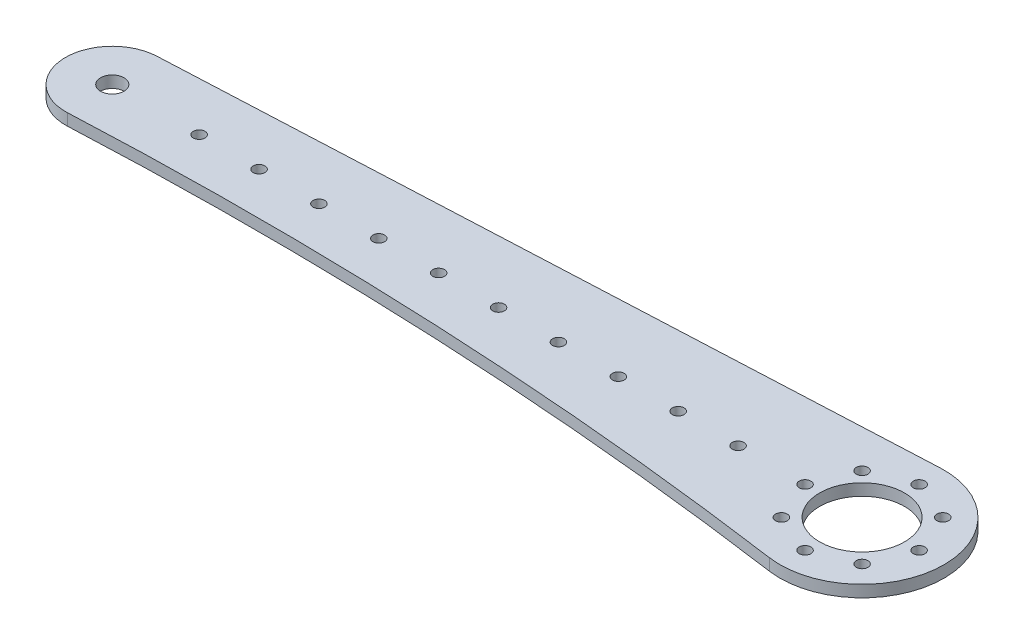
SolidWorks part; units mm, degrees
material "ABS"
ref_plane "Front Plane" through (0, 0, 0) normal (0, 0, 1) x (1, 0, 0)
ref_plane "Top Plane" through (0, 0, 0) normal (0, 1, 0) x (1, 0, 0)
ref_plane "Right Plane" through (0, 0, 0) normal (1, 0, 0) x (0, 0, -1)
sketch "Sketch2" plane through (0, 0, 0) normal (0, 1, 0) x (1, 0, 0)
  line L0 (-203.7953, 12.686) -> (-1.0418, 22.2006)
  line L1 (-1.0418, 22.2006) -> (0, 0) construction
  line L2 (-203.7953, 12.686) -> (-202.6047, -12.686) construction
  circle A0 centre (-203.2, 0) radius 12.7 construction
  circle A1 centre (0, 0) radius 22.225 construction
  circle A2 centre (-0.4465, 9.5145) radius 12.7 construction
  arc A3 (-203.7953, 12.686) -> (-202.6047, -12.686) centre (-203.2, 0) ccw
  arc A4 (-202.6047, -12.686) -> (-3.1072, -22.0067) centre (-152.5116, -1080.1634) cw
  arc A5 (-1.0418, 22.2006) -> (-3.1072, -22.0067) centre (0, 0) cw
  circle A6 centre (0, 0) radius 11.5
  circle A7 centre (0, 0) radius 11.5 construction
  circle A8 centre (-10.9329, -10.9329) radius 1.016 construction
  circle A9 centre (-15.4615, 0) radius 1.016 construction
  circle A10 centre (0, -15.4615) radius 1.016 construction
  circle A11 centre (10.9329, -10.9329) radius 1.016 construction
  circle A12 centre (15.4615, 0) radius 1.016 construction
  circle A13 centre (10.9329, 10.9329) radius 1.016 construction
  circle A14 centre (0, 15.4615) radius 1.016 construction
  circle A15 centre (-10.9329, 10.9329) radius 1.016 construction
  circle A16 centre (-10.9329, -10.9329) radius 1.016 construction
  circle A17 centre (-15.4615, 0) radius 1.016 construction
  circle A18 centre (0, -15.4615) radius 1.016 construction
  circle A19 centre (10.9329, -10.9329) radius 1.016 construction
  circle A20 centre (15.4615, 0) radius 1.016 construction
  circle A21 centre (10.9329, 10.9329) radius 1.016 construction
  circle A22 centre (0, 15.4615) radius 1.016 construction
  circle A23 centre (-10.9329, 10.9329) radius 1.016 construction
  circle A24 centre (-10.9329, 10.9329) radius 1.5875
  circle A25 centre (0, 15.4615) radius 1.5875
  circle A26 centre (10.9329, 10.9329) radius 1.5875
  circle A27 centre (15.4615, 0) radius 1.5875
  circle A28 centre (10.9329, -10.9329) radius 1.5875
  circle A29 centre (0, -15.4615) radius 1.5875
  circle A30 centre (-10.9329, -10.9329) radius 1.5875
  circle A31 centre (-15.4615, 0) radius 1.5875
  point P56 (0, 0)
  point P57 (0, 0)
  dimension "D1" = 25.4
  dimension "D2" = 44.45
  dimension "D3" = 3.175
extrude "Boss-Extrude1" add sketch "Sketch2" along normal mid plane 3.175
sketch "Sketch3" plane through (0, 0, 0) normal (0, 1, 0) x (1, 0, 0)
  line L0 (-179.6534, 0) -> (-33.6034, 0) construction
  line L1 (-22.7568, 0) -> (-33.6034, 0) construction
  line L2 (-190.5, 0) -> (-179.6534, 0) construction
  circle A0 centre (0, 0) radius 22.7568 construction
  circle A2 centre (-179.6534, 0) radius 1.5875
  circle A3 centre (-163.4256, 0) radius 1.5875
  circle A4 centre (-147.1978, 0) radius 1.5875
  circle A5 centre (-130.9701, 0) radius 1.5875
  circle A6 centre (-114.7423, 0) radius 1.5875
  circle A7 centre (-98.5145, 0) radius 1.5875
  circle A8 centre (-82.2867, 0) radius 1.5875
  circle A9 centre (-66.0589, 0) radius 1.5875
  circle A10 centre (-49.8312, 0) radius 1.5875
  circle A11 centre (-33.6034, 0) radius 1.5875
  arc A12 (-203.7953, 12.686) -> (-202.6047, -12.686) centre (-203.2, 0) ccw construction
  point P8 (-203.2, 0)
  point P9 (-190.1003, 0)
  point P12 (-71.7113, 0)
  point P33 (0, 0)
  dimension "D2" = 3.175
  dimension "D1" = 146.05
  dimension "D3" = 10
extrude "Cut-Extrude1" cut sketch "Sketch3" against normal through all both and the other way through all
sketch "Sketch4" plane through (0, 0, 0) normal (0, -1, 0) x (1, 0, 0)
  circle A0 centre (-203.2, 0) radius 3.175
  dimension "D1" = 6.35
extrude "Cut-Extrude2" cut sketch "Sketch4" against normal through all both and the other way through all
